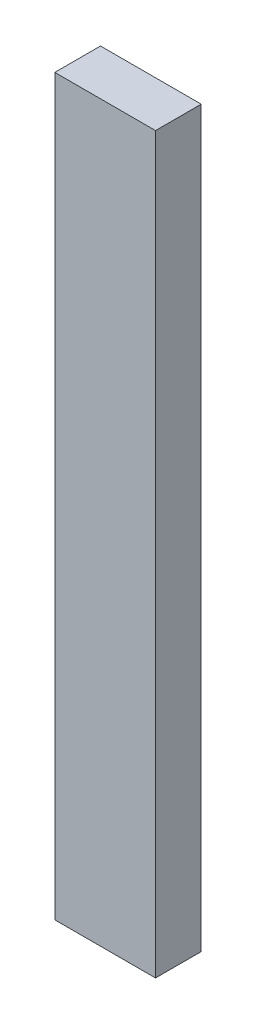
SolidWorks part; units mm, degrees
material "Pine"
ref_plane "Front Plane" through (0, 0, 0) normal (0, 0, 1) x (1, 0, 0)
ref_plane "Top Plane" through (0, 0, 0) normal (0, 1, 0) x (1, 0, 0)
ref_plane "Right Plane" through (0, 0, 0) normal (1, 0, 0) x (0, 0, -1)
sketch "Sketch1" plane through (0, 0, 0) normal (0, 1, 0) x (1, 0, 0)
  line L1 (0, 0) -> (54, 0)
  line L2 (0, 0) -> (0, 24.5)
  line L3 (0, 24.5) -> (54, 24.5)
  line L4 (54, 0) -> (54, 24.5)
  line L5 (0, 0) -> (54, 24.5) construction
  line L6 (0, 24.5) -> (54, 0) construction
  point P4 (27, 12.25)
  dimension "D1" = 24.5
  dimension "D2" = 54
extrude "Boss-Extrude1" add sketch "Sketch1" along normal blind 393.4
